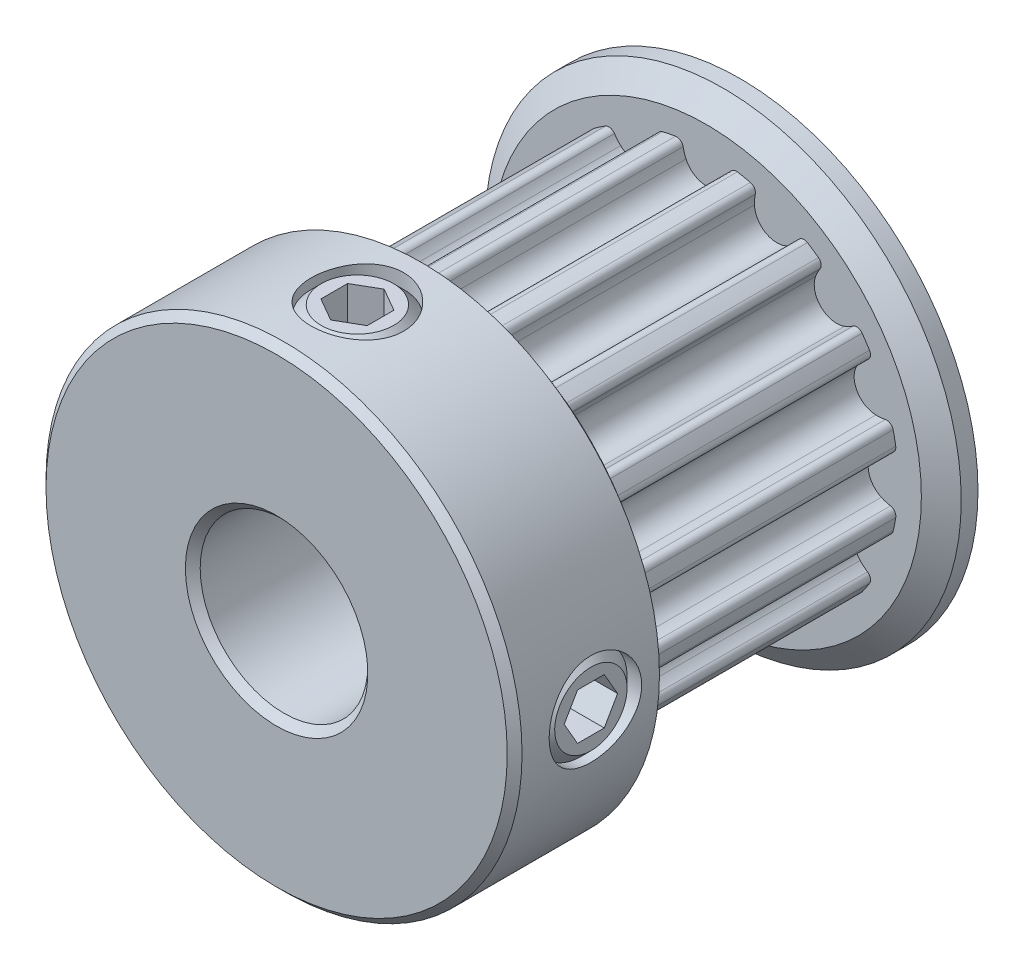
SolidWorks part; units mm, degrees
ref_plane "Front Plane" through (0, 0, 0) normal (0, 0, 1) x (1, 0, 0)
ref_plane "Top Plane" through (0, 0, 0) normal (0, 1, 0) x (1, 0, 0)
ref_plane "Right Plane" through (0, 0, 0) normal (1, 0, 0) x (0, 0, -1)
sketch "Sketch1" plane through (0, 0, 0) normal (0, 0, 1) x (1, 0, 0)
  line L1 (-2.553, 6.1245) -> (2.553, 6.1245) construction
  line L4 (0, 0) -> (0, 6.1245) construction
  line L5 (0, 6.1245) -> (0, 12.0668) construction
  line L6 (0, 7.6455) -> (2.9417, 7.0569) construction
  line L7 (2.9417, 7.0569) -> (3.8741, 6.6682) construction
  line L8 (2.9417, 7.0569) -> (2.553, 6.1245) construction
  line L9 (-2.9417, 7.0569) -> (-2.553, 6.1245) construction
  line L10 (-2.7951, 6.7052) -> (-3.7579, 9.015)
  line L11 (-3.7579, 9.015) -> (3.7579, 9.015)
  line L12 (3.7579, 9.015) -> (2.7951, 6.7052)
  circle A0 centre (0, 0) radius 7.6455 construction
  circle A1 centre (0, 0) radius 9.015 construction
  circle A2 centre (0, 0) radius 7.2645 construction
  arc A3 (-0.7739, 6.6229) -> (0.7739, 6.6229) centre (0, 6.9745) ccw
  arc A4 (-0.7739, 6.6229) -> (-0.8836, 6.9694) centre (0.61, 7.2516) cw
  arc A5 (-2.7951, 6.7052) -> (-1.1695, 7.1697) centre (0, 0) cw
  arc A6 (-0.8836, 6.9694) -> (-1.1695, 7.1697) centre (-1.1292, 6.923) ccw
  arc A7 (2.7951, 6.7052) -> (1.1695, 7.1697) centre (0, 0) ccw
  arc A8 (0.8836, 6.9694) -> (1.1695, 7.1697) centre (1.1292, 6.923) cw
  arc A9 (0.7739, 6.6229) -> (0.8836, 6.9694) centre (-0.61, 7.2516) ccw
  point P6 (0, 20.9083)
  point P11 (0, 7.6455)
  point P13 (0, 9.015)
  point P14 (0, 7.2645)
  dimension "D1" = 8.8416
  dimension "D2" = 4.4213
sketch "Sketch2" plane through (0, 0, 0) normal (1, 0, 0) x (0, 0, -1)
  line L0 (-8.775, 3.175) -> (8.775, 3.175)
  line L1 (-8.775, 3.175) -> (-8.775, 9.015)
  line L2 (-3.29, 9.015) -> (-8.775, 9.015)
  line L3 (-3.925, 3.175) -> (-3.925, 9.015) construction
  line L4 (-3.925, 9.015) -> (-2.655, 9.015) construction
  line L5 (-2.655, 9.015) -> (-2.655, 7.2645) construction
  line L6 (-2.655, 7.2645) -> (7.505, 7.2645)
  line L7 (7.505, 7.2645) -> (7.505, 9.015) construction
  line L8 (7.505, 9.015) -> (8.775, 9.015) construction
  line L9 (8.775, 9.015) -> (8.775, 3.175)
  line L10 (-8.775, 0) -> (8.775, 0) construction
  line L11 (8.14, 9.015) -> (7.505, 8.1398)
  line L12 (-2.655, 8.1398) -> (-3.29, 9.015)
  line L14 (-2.655, 8.1398) -> (-2.655, 7.2645)
  line L15 (7.505, 7.2645) -> (7.505, 8.1398)
  line L16 (8.14, 9.015) -> (8.775, 9.015)
  arc A0 (-2.655, 8.1398) -> (-3.29, 9.015) centre (-3.5757, 8.1398) ccw construction
  arc A1 (7.505, 8.1398) -> (8.14, 9.015) centre (8.4257, 8.1398) cw construction
  point P12 (-2.655, 8.1398)
  point P14 (-3.29, 9.015)
  point P20 (7.505, 8.1398)
  point P21 (8.14, 9.015)
  point P25 (7.505, 0)
  point P26 (-2.655, 0)
  dimension "OA" = 17.55
  dimension "Bore" = 6.35
  dimension "Outside Width" = 11.43
  dimension "Inside Width" = 10.16
revolve "Revolve1" add sketch "Sketch2" angle 360 mid plane about L10
sketch "Sketch3" plane through (0, 0, 0) normal (0, 0, 1) x (1, 0, 0)
  line L6 (3.7579, 9.015) -> (-3.7579, 9.015)
  line L7 (2.7951, 6.7052) -> (3.7579, 9.015)
  line L8 (-3.7579, 9.015) -> (-2.7951, 6.7052)
  line L9 (3.7579, 9.015) -> (-3.7579, 9.015)
  line L10 (2.7951, 6.7052) -> (3.7579, 9.015)
  line L11 (-3.7579, 9.015) -> (-2.7951, 6.7052)
  arc A8 (2.7951, 6.7052) -> (1.1695, 7.1697) centre (0, 0) ccw
  arc A9 (1.1695, 7.1697) -> (0.8836, 6.9694) centre (1.1292, 6.923) ccw
  arc A10 (0.7739, 6.6229) -> (0.8836, 6.9694) centre (-0.61, 7.2516) ccw
  arc A11 (-0.7739, 6.6229) -> (0.7739, 6.6229) centre (0, 6.9745) ccw
  arc A12 (-0.8836, 6.9694) -> (-0.7739, 6.6229) centre (0.61, 7.2516) ccw
  arc A13 (-0.8836, 6.9694) -> (-1.1695, 7.1697) centre (-1.1292, 6.923) ccw
  arc A14 (-1.1695, 7.1697) -> (-2.7951, 6.7052) centre (0, 0) ccw
  arc A15 (2.7951, 6.7052) -> (1.1695, 7.1697) centre (0, 0) ccw
  arc A16 (1.1695, 7.1697) -> (0.8836, 6.9694) centre (1.1292, 6.923) ccw
  arc A17 (0.7739, 6.6229) -> (0.8836, 6.9694) centre (-0.61, 7.2516) ccw
  arc A18 (-0.7739, 6.6229) -> (0.7739, 6.6229) centre (0, 6.9745) ccw
  arc A19 (-0.8836, 6.9694) -> (-0.7739, 6.6229) centre (0.61, 7.2516) ccw
  arc A20 (-0.8836, 6.9694) -> (-1.1695, 7.1697) centre (-1.1292, 6.923) ccw
  arc A21 (-1.1695, 7.1697) -> (-2.7951, 6.7052) centre (0, 0) ccw
  dimension "D1" = 0
extrude "Cut-Extrude1" cut sketch "Sketch3" against normal up to vertex (7.505 mm away) from vertex up to point (0, 7.2645, -7.505) starting at point (0, 7.2645, 2.655)
pattern_circular "CirPattern1" count 16 over 360 about axis through (0, 0, 8.775) along (0, 0, 1) of "Cut-Extrude1"
sketch "Sketch4" plane through (0, 0, 0) normal (1, 0, 0) x (0, -1, 0)
  line L0 (0, -2.655) -> (0, -8.775) construction
  line L1 (-3.175, -8.775) -> (3.175, -8.775) construction
  line L2 (8.1398, -2.655) -> (-8.1398, -2.655) construction
  circle A0 centre (0, -5.715) radius 1.7526
extrude "Cut-Extrude2" cut sketch "Sketch4" along normal through all
ref_plane "Plane1" through (0, 0, 5.715) normal (0, 0, 1) x (1, 0, 0)
sketch "Sketch5" plane through (0, 0, 5.715) normal (0, 0, 1) x (1, 0, 0)
  line L0 (0, 0) -> (0, 9.015) construction
  line L1 (3.175, -1.3716) -> (3.175, 0)
  line L2 (3.556, -1.7526) -> (8.462, -1.7526)
  line L3 (3.175, 0) -> (9.015, 0) construction
  line L4 (3.175, 0) -> (8.843, 0)
  line L5 (8.843, 0) -> (8.843, -1.3716)
  line L6 (3.556, -1.7526) -> (3.175, -1.3716)
  line L7 (8.843, -1.3716) -> (8.462, -1.7526)
  circle A0 centre (0, 0) radius 9.015 construction
  circle A1 centre (0, 0) radius 3.175 construction
  point P2 (3.175, -1.7526)
  point P11 (8.843, -1.7526)
revolve "Revolve2" add sketch "Sketch5" angle 360 mid plane about L4
sketch "Sketch6" plane through (8.843, 5.3841, 0) normal (-1, 0, 0) x (0, -1, 0)
  line L1 (5.3841, 6.7269) -> (4.5078, 6.2209)
  line L2 (4.5078, 6.2209) -> (4.5078, 5.2091)
  line L3 (4.5078, 5.2091) -> (5.3841, 4.7031)
  line L4 (5.3841, 4.7031) -> (6.2604, 5.2091)
  line L5 (6.2604, 5.2091) -> (6.2604, 6.2209)
  line L6 (6.2604, 6.2209) -> (5.3841, 6.7269)
  circle A0 centre (5.3841, 5.715) radius 0.8763 construction
  dimension "D1" = 1.7526
extrude "Cut-Extrude3" cut sketch "Sketch6" along normal blind 1.3144
pattern_circular "CirPattern3" count 2 over 90 about axis through (0, 0, 8.775) along (0, 0, 1) of "Cut-Extrude2", "Revolve2", "Cut-Extrude3"
chamfer "Chamfer1" distance 0.2807 angle 45 2 edges at (3.175, 0, 8.775) (9.015, 0, 8.775)
ref_axis "Center Axis 1" through (0, 0, -8.775) along (0, 0, 1)
ref_plane "Contact Plane 1" through (0, 0, 8.775) normal (0, 0, 1) x (1, 0, 0)
ref_plane "Contact Plane 2" through (0, 0, -8.775) normal (0, 0, -1) x (-1, 0, 0)
ref_axis "Axis1" through (0, 0, -8.775) along (0, 0, 1)
equation "\"D2@Sketch1\"= \"D1@Sketch1\" / 2"
equation "\"D1@Sketch6\" = \"Set Screw@Sketch4\" / 2"
equation "\"D1@Cut-Extrude3\" = \"D1@Sketch6\"*.75"
